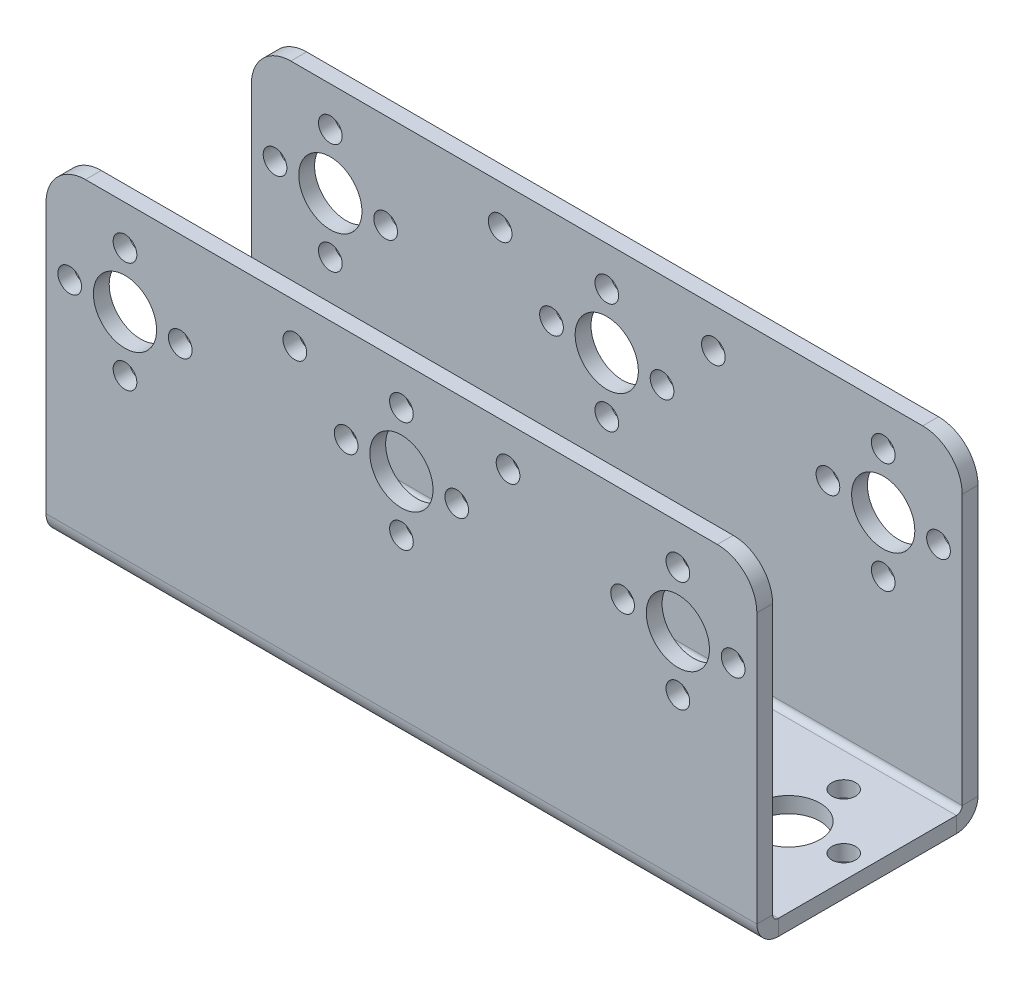
SolidWorks part; units mm, degrees
note: The reader was unsure of these and kept them because the rebuilt part matched: flange length of "Bordo-Flangia1".
ref_plane "Piano frontale" through (0, 0, 0) normal (0, 0, 1) x (1, 0, 0)
ref_plane "Piano superiore" through (0, 0, 0) normal (0, 1, 0) x (1, 0, 0)
ref_plane "Piano destro" through (0, 0, 0) normal (1, 0, 0) x (0, 0, -1)
sketch "Schizzo1" plane through (0, 0, 0) normal (0, 1, 0) x (1, 0, 0)
  line L1 (-45, -14) -> (45, -14)
  line L2 (-45, -14) -> (-45, 14)
  line L3 (-45, 14) -> (45, 14)
  line L4 (45, -14) -> (45, 14)
  line L5 (-45, -14) -> (45, 14) construction
  line L6 (-45, 14) -> (45, -14) construction
  point P0 (0, 0)
  dimension "D1" = 28
  dimension "D2" = 90
base flange "Base-Flangia1" sketch "Schizzo1" thickness 2 reverse thickness direction yes parameters "D1"=0.7366
edge flange "Bordo-Flangia1" sketch "Schizzo2" flange profiles "Schizzo2", "Schizzo3" flange angle 90 flange length 41.86 flange position material inside bend radius 0.7366 thickness 2 relief rectangular parameters "D6"=10, "D8"=1
sketch "Schizzo2" plane through (0, 2, 14) normal (0, 0, -1) x (-1, 0, 0)
  line L2 (-45, 0) -> (-45, 39.86)
  line L3 (-45, 39.86) -> (45, 39.86)
  line L4 (45, 39.86) -> (45, 0)
  line L5 (45, 0) -> (-45, 0) construction
  line L6 (45, 0) -> (-45, 0)
  circle A0 centre (-35, 27.86) radius 4
  circle A1 centre (0, 27.86) radius 4
  circle A2 centre (35, 27.86) radius 4
  circle A3 centre (28, 27.86) radius 1.5
  circle A4 centre (35, 34.86) radius 1.5
  circle A5 centre (42, 27.86) radius 1.5
  circle A6 centre (35, 20.86) radius 1.5
  circle A7 centre (0, 20.86) radius 1.5
  circle A8 centre (7, 27.86) radius 1.5
  circle A9 centre (0, 34.86) radius 1.5
  circle A10 centre (-7, 27.86) radius 1.5
  circle A11 centre (-28, 27.86) radius 1.5
  circle A12 centre (-35, 34.86) radius 1.5
  circle A13 centre (-35, 20.86) radius 1.5
  circle A14 centre (-42, 27.86) radius 1.5
  circle A15 centre (-13.5, 34.86) radius 1.5
  circle A16 centre (13.5, 34.86) radius 1.5
  point P36 (0, 0)
  dimension "D1" = 8
  dimension "D2" = 3
  dimension "D3" = 7
  dimension "D4" = 7
  dimension "D5" = 7
  dimension "D6" = 7
  dimension "D7" = 7
  dimension "D8" = 7
  dimension "D9" = 7
  dimension "D10" = 7
  dimension "D11" = 12
  dimension "D12" = 10
  dimension "D13" = 10
  dimension "D14" = 13.5
  dimension "D15" = 13.5
sketch "Schizzo3" plane through (0, 2, -14) normal (0, 0, 1) x (1, 0, 0)
  line L0 (45, 0) -> (-45, 0) construction
  line L1 (45, 0) -> (-45, 0)
  line L2 (45, 0) -> (45, 39.86)
  line L3 (45, 39.86) -> (-45, 39.86)
  line L4 (-45, 39.86) -> (-45, 0)
  circle A0 centre (35, 20.86) radius 1.5 construction
  circle A1 centre (42, 27.86) radius 1.5 construction
  circle A2 centre (35, 34.86) radius 1.5 construction
  circle A3 centre (35, 27.86) radius 4 construction
  circle A4 centre (28, 27.86) radius 1.5 construction
  circle A5 centre (0, 20.86) radius 1.5 construction
  circle A6 centre (7, 27.86) radius 1.5 construction
  circle A7 centre (0, 34.86) radius 1.5 construction
  circle A8 centre (0, 27.86) radius 4 construction
  circle A9 centre (-7, 27.86) radius 1.5 construction
  circle A10 centre (-28, 27.86) radius 1.5 construction
  circle A11 centre (-35, 20.86) radius 1.5 construction
  circle A12 centre (-35, 34.86) radius 1.5 construction
  circle A13 centre (-35, 27.86) radius 4 construction
  circle A14 centre (-42, 27.86) radius 1.5 construction
  circle A15 centre (35, 20.86) radius 1.5
  circle A16 centre (42, 27.86) radius 1.5
  circle A17 centre (35, 34.86) radius 1.5
  circle A18 centre (35, 27.86) radius 4
  circle A19 centre (28, 27.86) radius 1.5
  circle A20 centre (0, 20.86) radius 1.5
  circle A21 centre (7, 27.86) radius 1.5
  circle A22 centre (0, 34.86) radius 1.5
  circle A23 centre (0, 27.86) radius 4
  circle A24 centre (-7, 27.86) radius 1.5
  circle A25 centre (-28, 27.86) radius 1.5
  circle A26 centre (-35, 20.86) radius 1.5
  circle A27 centre (-35, 34.86) radius 1.5
  circle A28 centre (-35, 27.86) radius 4
  circle A29 centre (-42, 27.86) radius 1.5
  circle A30 centre (13.5, 34.86) radius 1.5 construction
  circle A31 centre (-13.5, 34.86) radius 1.5 construction
  circle A32 centre (13.5, 34.86) radius 1.5
  circle A33 centre (-13.5, 34.86) radius 1.5
bend "PiegaturaBordo1" bend radius 0.7366 bend angle 90 parameters "D5"=1
bend "PiegaturaBordo2" bend radius 0.7366 bend angle 90 parameters "D5"=2
fillet "Raccordo1" radius 5 4 edges at (-45, 41.86, -13) (-45, 41.86, 13) (45, 41.86, -13) (45, 41.86, 13)
sketch "Schizzo4" plane through (0, 2, 0) normal (0, 1, 0) x (1, 0, 0)
  line L0 (-45, 11.2634) -> (-45, -11.2634) construction
  line L1 (45, -11.2634) -> (45, 11.2634) construction
  circle A0 centre (-35, 0) radius 4
  circle A1 centre (0, 0) radius 4
  circle A2 centre (35, 0) radius 4
  circle A3 centre (-35, 7) radius 1.5
  circle A4 centre (-28, 0) radius 1.5
  circle A5 centre (-35, -7) radius 1.5
  circle A6 centre (-42, 0) radius 1.5
  circle A7 centre (-7, 0) radius 1.5
  circle A8 centre (0, 7) radius 1.5
  circle A9 centre (7, 0) radius 1.5
  circle A10 centre (0, -7) radius 1.5
  circle A11 centre (35, -7) radius 1.5
  circle A12 centre (28, 0) radius 1.5
  circle A13 centre (35, 7) radius 1.5
  circle A14 centre (42, 0) radius 1.5
  dimension "D1" = 8
  dimension "D2" = 3
  dimension "D3" = 7
  dimension "D4" = 7
  dimension "D5" = 7
  dimension "D6" = 7
  dimension "D7" = 7
  dimension "D8" = 7
  dimension "D9" = 7
  dimension "D10" = 7
  dimension "D11" = 10
  dimension "D12" = 10
extrude "Cut-Extrude1" cut sketch "Schizzo4" against normal up to next normal cut yes
sketch "Linee di piegatura3" [suppressed] plane through (0, 0, 0) normal (0, 1, 0) x (1, 0, 0)
sketch "Casella di contorno3" [suppressed] plane through (0, 0, 0) normal (0, 1, 0) x (1, 0, 0)
sheet metal parameters "Lamiera1" thickness 2 parameters "D1"=0.7366
flat pattern "Ripetizione piatta3" [suppressed]
sketch "Linee di piegatura4" plane through (0, 0, 0) normal (0, 1, 0) x (1, 0, 0)
sketch3d "Casella di contorno4" [suppressed]
  line L0 (-45, 14, 0) -> (45, 14, 0) construction
  line L1 (-45, -14, 0) -> (45, -14, 0) construction
  line L2 (-45, 14, 0) -> (-45, -14, 0) construction
  line L3 (45, 14, 0) -> (45, -14, 0) construction
sheet metal parameters "Lamiera4" thickness 2 parameters "D1"=0.7366
flat pattern "Ripetizione piatta3"
sketch "Linee di piegatura4" plane through (0, 0, 0) normal (0, -1, 0) x (-1, 0, 0)
  line L0 (45, 12.6273) -> (-45, 12.6273) construction
  line L1 (-45, -12.6273) -> (45, -12.6273) construction
  line L2 (45, 12.6273) -> (-45, 12.6273) construction
  line L3 (-45, -12.6273) -> (45, -12.6273) construction
sketch3d "Casella di contorno4" [suppressed]
  line L0 (-45, -53.1146, 0) -> (-45, 53.1146, 0) construction
  line L1 (45, -53.1146, 0) -> (45, 53.1146, 0) construction
  line L2 (-45, -53.1146, 0) -> (45, -53.1146, 0) construction
  line L3 (-45, 53.1146, 0) -> (45, 53.1146, 0) construction
bend of the flat pattern "Appiattito-<PiegaturaBordo1>1"
bend of the flat pattern "Appiattito-<PiegaturaBordo2>1"
sheet metal parameters "Lamiera5" thickness 2 parameters "D1"=0.7366
flat pattern "Ripetizione piatta3"
sketch "Linee di piegatura4" plane through (0, 0, 0) normal (0, -1, 0) x (-1, 0, 0)
  line L0 (45, 12.6273) -> (-45, 12.6273) construction
  line L1 (-45, -12.6273) -> (45, -12.6273) construction
  line L2 (45, 12.6273) -> (-45, 12.6273) construction
  line L3 (-45, -12.6273) -> (45, -12.6273) construction
sketch3d "Casella di contorno4" [suppressed]
  line L0 (-45, -53.1146, 0) -> (-45, 53.1146, 0) construction
  line L1 (45, -53.1146, 0) -> (45, 53.1146, 0) construction
  line L2 (-45, -53.1146, 0) -> (45, -53.1146, 0) construction
  line L3 (-45, 53.1146, 0) -> (45, 53.1146, 0) construction
bend of the flat pattern "Appiattito-<PiegaturaBordo1>1"
bend of the flat pattern "Appiattito-<PiegaturaBordo2>1"
